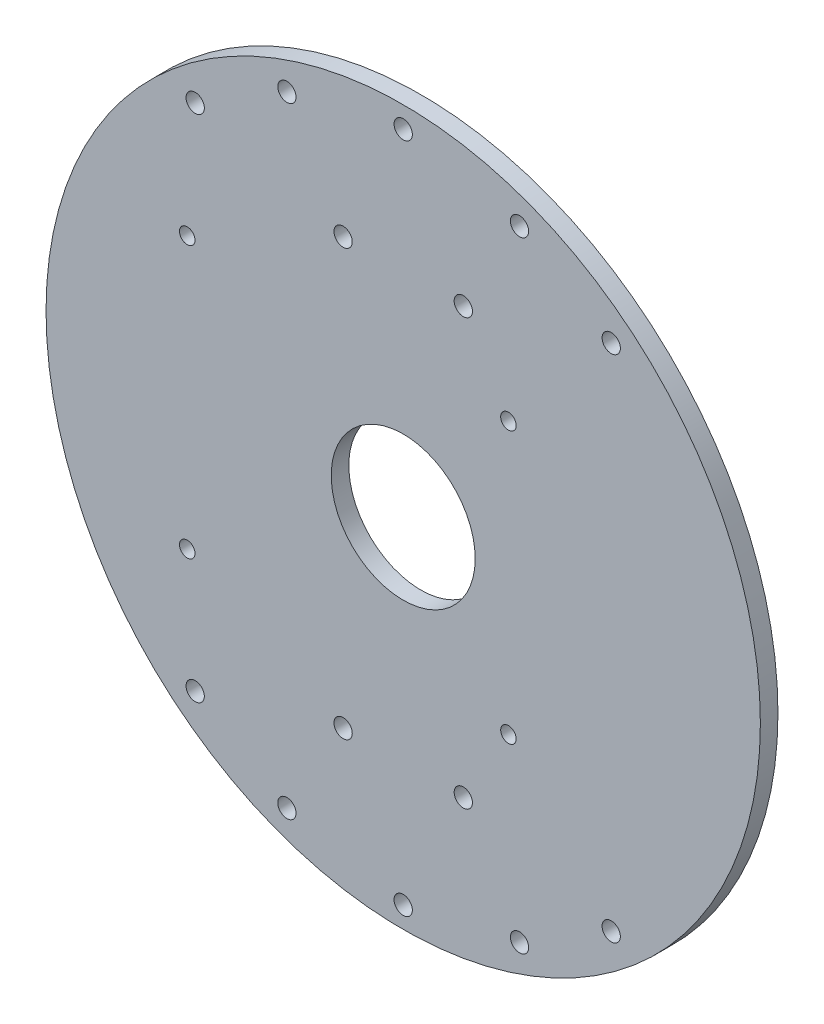
SolidWorks part; units mm, degrees
ref_plane "Front Plane" through (0, 0, 0) normal (0, 0, 1) x (1, 0, 0)
ref_plane "Top Plane" through (0, 0, 0) normal (0, 1, 0) x (1, 0, 0)
ref_plane "Right Plane" through (0, 0, 0) normal (1, 0, 0) x (0, 0, -1)
sketch "Sketch1" plane through (0, 0, 0) normal (0, 0, 1) x (-1, 0, 0)
  line L0 (54.1686, -24.1336) -> (57.6686, -24.1336) construction
  line L1 (57.6686, -24.1336) -> (57.6686, 24.8664) construction
  line L2 (15.1686, 64.8664) -> (15.1686, -64.1336) construction
  line L5 (79.6686, 0.3664) -> (-49.3314, 0.3664) construction
  line L6 (54.1686, -24.1336) -> (54.1686, 24.8664) construction
  line L7 (54.1686, 24.8664) -> (-3.8314, 24.8664) construction
  line L8 (-3.8314, 24.8664) -> (-3.8314, -24.1336) construction
  line L9 (-3.8314, -24.1336) -> (54.1686, -24.1336) construction
  line L12 (57.6686, 24.8664) -> (54.1686, 24.8664) construction
  line L13 (-3.8314, -24.1336) -> (-27.3314, -24.1336) construction
  line L14 (-27.3314, -24.1336) -> (-27.3314, 24.8664) construction
  line L15 (-27.3314, 24.8664) -> (-3.8314, 24.8664) construction
  circle A1 centre (15.1686, 0.3664) radius 64.5
  circle A2 centre (15.1686, -60.2836) radius 1.65
  circle A3 centre (15.1686, 61.0164) radius 1.65
  circle A5 centre (26.0186, -38.0586) radius 1.65
  circle A7 centre (4.3186, -38.0586) radius 1.65
  circle A8 centre (26.0186, 38.7914) radius 1.65
  circle A9 centre (4.3186, 38.7914) radius 1.65
  circle A10 centre (15.1686, 0.3664) radius 13
  circle A11 centre (54.1686, -24.1336) radius 1.4
  circle A12 centre (54.1686, 24.8664) radius 1.4
  circle A13 centre (-3.8314, -24.1336) radius 1.4
  circle A14 centre (-3.8314, 24.8664) radius 1.4
  circle A15 centre (-5.8314, 56.3664) radius 1.65
  circle A16 centre (-22.3949, 46.3664) radius 1.65
  circle A17 centre (36.1686, 56.3664) radius 1.65
  circle A18 centre (52.7321, 46.3664) radius 1.65
  circle A19 centre (52.7321, -45.6336) radius 1.65
  circle A20 centre (36.1686, -55.6336) radius 1.65
  circle A21 centre (-5.8314, -55.6336) radius 1.65
  circle A22 centre (-22.3949, -45.6336) radius 1.65
  dimension "D3" = 23.5
  dimension "D1" = 3.3
  dimension "D4" = 10.85
  dimension "D9" = 26
  dimension "D10" = 3.3
  dimension "D11" = 56
  dimension "D12" = 46
  dimension "D13" = 2.8
  dimension "D20" = 129
  dimension "D2" = 3.5
  dimension "D5" = 60.65
  dimension "D6" = 21.7
  dimension "D7" = 22.225
  dimension "D8" = 22.225
  dimension "D14" = 21
  dimension "D18" = 85
  dimension "D19" = 49
  dimension "D22" = 22
  dimension "D23" = 22
extrude "Boss-Extrude2" add sketch "Sketch1" along normal blind 3.175
